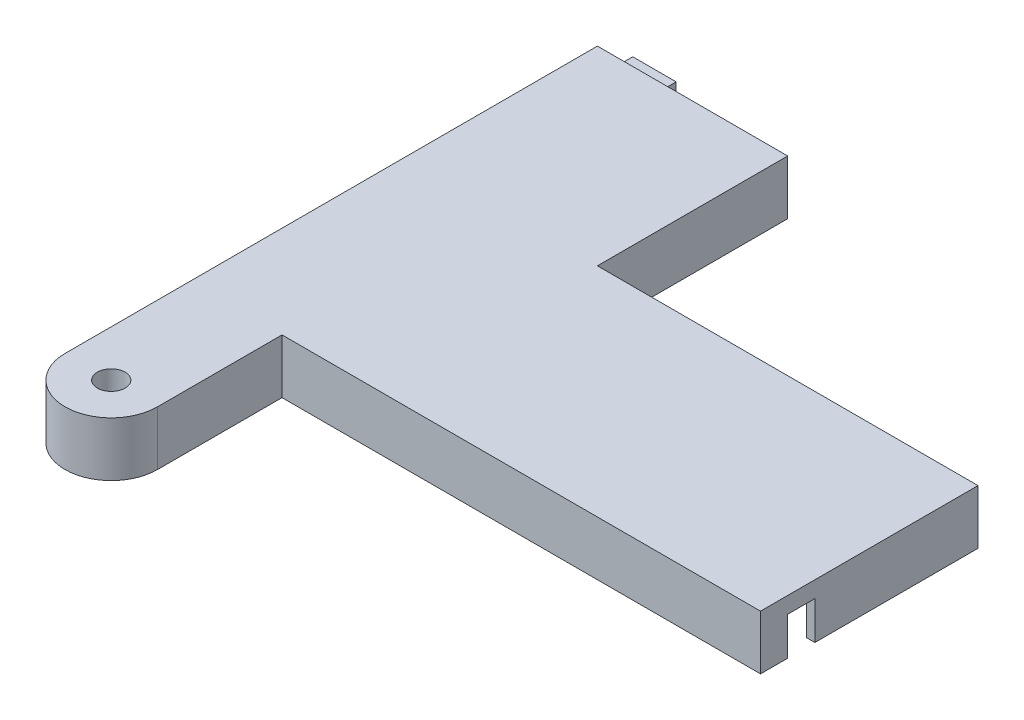
SolidWorks part; units mm, degrees
ref_plane "Front Plane" through (0, 0, 0) normal (0, 0, 1) x (1, 0, 0)
ref_plane "Top Plane" through (0, 0, 0) normal (0, 1, 0) x (1, 0, 0)
ref_plane "Right Plane" through (0, 0, 0) normal (1, 0, 0) x (0, 0, -1)
sketch "CornerrSketch1" plane through (0, 0, 0) normal (0, 1, 0) x (1, 0, 0)
  line L0 (0, 195.825) -> (70, 195.825)
  line L5 (70, 195.825) -> (70, 125.825)
  line L6 (70, 125.825) -> (210, 125.825)
  line L7 (210, 45.825) -> (210, 125.825)
  line L11 (34, 0) -> (34, 45.825)
  line L12 (34, 45.825) -> (210, 45.825)
  line L13 (0, 195.825) -> (0, 0)
  arc A0 (0, 0) -> (34, 0) centre (17, 0) ccw
  point P2 (35, 195.825)
  dimension "D3" = 34
  dimension "D4" = 70
  dimension "D2" = 80
  dimension "D1" = 45.825
  dimension "D6" = 210
  dimension "D5" = 150
extrude "CornerBoss-Extrude1" add sketch "CornerrSketch1" along normal blind 20
shell "Shell4" thickness 3 removed face at (78.5, 0, -89.7438)
sketch "PadSketch2" plane through (0, 17, 0) normal (0, -1, 0) x (1, 0, 0)
  circle A0 centre (17, 0) radius 12
  dimension "D1" = 24
extrude "PadBoss-Extrude2" add sketch "PadSketch2" along normal blind 10
sketch "StepperShaftHoleCutSketch3" plane through (0, 7, 0) normal (0, -1, 0) x (1, 0, 0)
  circle A0 centre (17, 0) radius 5.1
  dimension "D1" = 10.2
extrude "StepperShaftHoleCut-Extrude1" cut sketch "StepperShaftHoleCutSketch3" against normal through all
sketch "ThreadedNutMountHolesSketch4" plane through (0, 7, 0) normal (0, -1, 0) x (-1, 0, 0)
  circle A8 centre (-17, 8) radius 2
  circle A9 centre (-17, -8) radius 2
  circle A10 centre (-25, 0) radius 2
  circle A11 centre (-9, 0) radius 2
  dimension "D1" = 4
  dimension "D3" = 16
  dimension "D4" = 8
  dimension "D5" = 16
extrude "ThreadedNutMountHolesCut-Extrude2" cut sketch "ThreadedNutMountHolesSketch4" against normal blind 10
sketch "BRPegHoleSketch1" plane through (210, 0, 0) normal (1, 0, 0) x (0, 0, -1)
  line L1 (55.825, 14) -> (65.825, 14)
  line L2 (55.825, 14) -> (55.825, 0)
  line L3 (55.825, 0) -> (65.825, 0)
  line L4 (65.825, 14) -> (65.825, 0)
  line L6 (45.825, 0) -> (125.825, 0) construction
  line L7 (45.825, 20) -> (45.825, 0) construction
  dimension "D2" = 10
  dimension "D3" = 14
  dimension "D1" = 10
extrude "BRPegHoleCut-Extrude1" cut sketch "BRPegHoleSketch1" against normal blind 3
sketch "TopPegSketch2" plane through (0, 0, -195.825) normal (0, 0, -1) x (-1, 0, 0)
  line L0 (0, 20) -> (0, 0) construction
  line L1 (-19.9, 13.9) -> (-10.1, 13.9)
  line L2 (-19.9, 13.9) -> (-19.9, 0)
  line L3 (-19.9, 0) -> (-10.1, 0)
  line L4 (-10.1, 13.9) -> (-10.1, 0)
  line L6 (-70, 0) -> (0, 0) construction
  dimension "D2" = 13.9
  dimension "D3" = 9.8
  dimension "D1" = 10.1
extrude "TopPegBoss-Extrude1" add sketch "TopPegSketch2" along normal blind 3
sketch "TopPegCapSketch3" plane through (0, 0, -198.825) normal (0, 0, -1) x (-1, 0, 0)
  line L1 (-22.9, 17) -> (-6.9, 17)
  line L2 (-22.9, 17) -> (-22.9, 0)
  line L3 (-22.9, 0) -> (-6.9, 0)
  line L4 (-6.9, 17) -> (-6.9, 0)
  line L5 (-19.9, 0) -> (-10.1, 0) construction
  line L7 (-19.9, 13.9) -> (-19.9, 0) construction
  dimension "D1" = 16
  dimension "D3" = 17
  dimension "D2" = 3
extrude "TopPegCapBoss-Extrude2" add sketch "TopPegCapSketch3" along normal blind 3.1
sketch "CenterPegHoleCutSketch1" plane through (0, 0, -125.825) normal (0, 0, -1) x (-1, 0, 0)
  line L0 (-210, 0) -> (-70, 0) construction
  line L1 (-180, 14) -> (-170, 14)
  line L2 (-180, 14) -> (-180, 0)
  line L3 (-180, 0) -> (-170, 0)
  line L4 (-170, 14) -> (-170, 0)
  line L6 (-70, 20) -> (-70, 0) construction
  dimension "D2" = 10
  dimension "D1" = 14
  dimension "D3" = 100
extrude "CenterPegHoleCut-Extrude1" cut sketch "CenterPegHoleCutSketch1" against normal blind 3
equation "\"RailThickness\"= .125in'Spec"
equation "\"StepperMountingHoleDistance\"= 31mm'Spec"
equation "\"StepperMountingHoleOffsetFromLeftOrRightSide\"= \"StepperMountingHoleOffsetFromItsSide\" + \"RailThickness\""
equation "\"StepperMountingHoleOffsetFromItsSide\"= 5.5mm'Spec"
equation "\"FrontBackRailLength\"= 510mm"
equation "\"DistanceBetweenLeftToRightStepperHoles\"= \"FrontBackRailLength\" - \"StepperMountingHoleOffsetFromLeftOrRightSide\" * 2 - \"StepperMountingHoleDistance\"'Equals 461.65"
equation "\"BedThickness\"= 20mm"
equation "\"BedLLongSide\"= \"BedThirdSize\" * 3'Equals 210"
equation "\"BedLShortSide\"= \"BedThirdSize\" * 2'Equals 140"
equation "\"BedLWidth\"= \"BedThirdSize\"'Equals 70"
equation "\"D4@CornerrSketch1\"=\"BedLWidth\" + \"BedIncreasedByLength\"/2"
equation "\"BedIncreasedByWidth\"= 20mm"
equation "\"BedIncreasedByLength\"= 0mm"
equation "\"BedThirdSize\"= 70mm"
equation "\"BedWidth\"= \"BedInnerSquareWidth\" + \"BedLWidth\" * 2 + \"BedIncreasedByWidth\"'Equals 370"
equation "\"BedInnerSquareWidth\"= \"BedThirdSize\" * 3'Equals 210"
equation "\"StandardWallThickness\"= 3mm"
equation "\"D2@BRPegHoleSketch1\"=\"BedPegHoleWidth\""
equation "\"D1@BRPegHoleSketch1\"=\"BedTopPegOffsetFromSide\" "
equation "\"D3@BRPegHoleSketch1\"=\"BedPegHoleHeight\""
equation "\"D1@BRPegHoleCut-Extrude1\" = \"StandardWallThickness\""
equation "\"D2@TopPegSketch2\"=\"BedPegHeight\""
equation "\"D1@TopPegBoss-Extrude1\" = \"StandardWallThickness\""
equation "\"D3@TopPegCapSketch3\"=\"BedPegCapHeight\""
equation "\"D1@TopPegCapSketch3\"=\"BedPegCapWidth\""
equation "\"D1@TopPegCapBoss-Extrude2\"=\"BedPegBoss\""
equation "\"D2@TopPegCapSketch3\"=\"StandardWallThickness\""
equation "\"DistanceFromBedSideToStepperHole\"= ( \"DistanceBetweenLeftToRightStepperHoles\" - \"BedWidth\" ) / 2'Equals 45.825"
equation "\"DistanceFromBedFrontToFirstLeftStepperHole\"= \"LeadScrewNutPadSize\" + 10mm'Equals 34"
equation "\"D3@CornerrSketch1\"=\"DistanceFromBedFrontToFirstLeftStepperHole\""
equation "\"LeadScrewNutPadSize\"= \"LeadScrewNutMountingHoleFlangeDiameter\" + 2mm'Equals 24"
equation "\"D1@PadSketch2\" = \"LeadScrewNutPadSize\""
equation "\"D1@StepperShaftHoleCutSketch3\"=\"LeadScrewNutInnerShaftFlangeDiameter\""
equation "\"D2@CornerrSketch1\"=\"BedLWidth\" + \"BedIncreasedByWidth\"/2"
equation "\"D6@CornerrSketch1\"=\"BedLLongSide\""
equation "\"D1@TopPegSketch2\"=\"BedTopPegOffsetFromSide\" + .1mm"
equation "\"D1@CornerrSketch1\"=\"DistanceFromBedSideToStepperHole\""
equation "\"D5@CornerrSketch1\"=\"BedLShortSide\" + \"BedIncreasedByWidth\"/2"
equation "\"LeadScrewNutInnerShaftFlangeDiameter\"= 10.2mm'Spec"
equation "\"LeadScrewNutMountHoleDiameter\"= \"M3HeatInsertHoleDiameter\""
equation "\"LeadScrewNutMountingHoleFlangeDiameter\"= 22mm'Spec"
equation "\"LeadScrewNutMountingHoleDistance\"= 16mm'Spec"
equation "\"D1@ThreadedNutMountHolesSketch4\"=\"LeadScrewNutMountHoleDiameter\""
equation "\"D2@ThreadedNutMountHolesSketch4\"=\"LeadScrewNutMountingHoleDistance\"/2"
equation "\"D3@ThreadedNutMountHolesSketch4\"=\"LeadScrewNutMountingHoleDistance\""
equation "\"D4@ThreadedNutMountHolesSketch4\"=\"LeadScrewNutMountingHoleDistance\"/2"
equation "\"D5@ThreadedNutMountHolesSketch4\"=\"LeadScrewNutMountingHoleDistance\""
equation "\"LeadScrewNutPadDepth\"= \"BedThickness\" / 2'Equals 10"
equation "\"D1@PadBoss-Extrude2\"=\"LeadScrewNutPadDepth\""
equation "\"D1@ThreadedNutMountHolesCut-Extrude2\"= \"LeadScrewNutPadDepth\""
equation "\"BedPegHoleWidth\"= 10mm"
equation "\"BedPegHoleHeight\"= \"BedThickness\" - \"StandardWallThickness\" * 2'Equals 14"
equation "\"BedPegWidth\"= \"BedPegHoleWidth\" - .1mm * 2'For easier assembly"
equation "\"BedPegHeight\"= \"BedPegHoleHeight\" - .1mm'For easier assembly"
equation "\"BedTopPegOffsetFromSide\"= 10mm"
equation "\"BedPegBoss\"= \"StandardWallThickness\" + .1mm'For easier assembly"
equation "\"BedPegCapHeight\"= \"BedThickness\" - \"StandardWallThickness\"'Equals 17"
equation "\"BedPegCapWidth\"= \"BedThickness\" / 2 + \"StandardWallThickness\" * 2'Equals 16"
equation "\"D3@TopPegSketch2\"=\"BedPegWidth\""
equation "\"D1@CenterPegHoleCutSketch1\" = \"BedPegHoleHeight\""
equation "\"D2@CenterPegHoleCutSketch1\" = \"BedPegHoleWidth\""
equation "\"D3@CenterPegHoleCutSketch1\"= \"BedInnerSquareWidth\" / 2 - \"BedPegHoleWidth\" / 2"
equation "\"D1@CenterPegHoleCut-Extrude1\"=\"StandardWallThickness\""
equation "\"M3HeatInsertHoleDiameter\"= 4mm'Spec"
